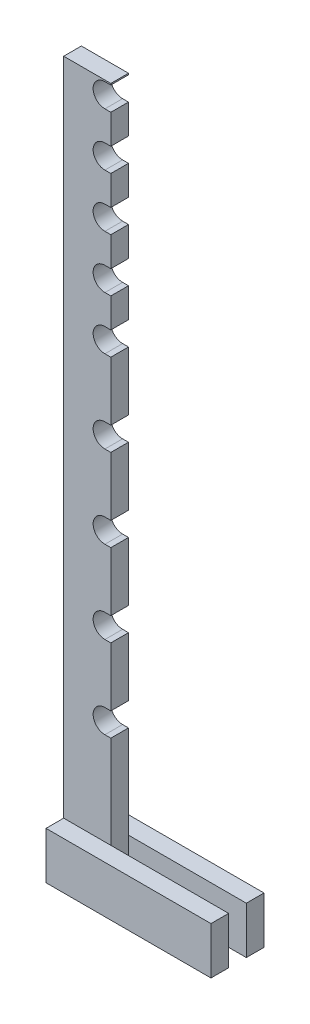
SolidWorks part; units mm, degrees
material "Maple"
ref_plane "Front" through (0, 0, 0) normal (0, 0, 1) x (1, 0, 0)
ref_plane "Top" through (0, 0, 0) normal (0, 1, 0) x (1, 0, 0)
ref_plane "Right" through (0, 0, 0) normal (1, 0, 0) x (0, 0, -1)
sketch "Sketch1" plane through (0, 0, 0) normal (0, 0, 1) x (1, 0, 0)
  line L10 (0, 0) -> (50.8, 0)
  line L14 (0, 0) -> (0, 762)
  line L15 (0, 762) -> (50.8, 762)
  line L16 (50.8, 0) -> (50.8, 762)
  dimension "D1" = 762
  dimension "D2" = 50.8
extrude "Boss-Extrude1" add sketch "Sketch1" along normal mid plane 19.05
sketch "Sketch3" plane through (0, 0, 9.525) normal (0, 0, 1) x (1, 0, 0)
  line L1 (0, 0) -> (177.8, 0)
  line L2 (0, 0) -> (0, 50.8)
  line L3 (0, 50.8) -> (177.8, 50.8)
  line L4 (177.8, 0) -> (177.8, 50.8)
  dimension "D1" = 50.8
  dimension "D2" = 177.8
extrude "Boss-Extrude2" add sketch "Sketch3" along normal blind 19.05 separate body
mirror "Mirror1" about plane through (0, 0, 0) normal (0, 0, 1) of bodies 182
sketch "Sketch2" plane through (0, 0, 9.525) normal (0, 0, 1) x (1, 0, 0)
  line L2 (44.45, 163.576) -> (50.8, 163.576) construction
  line L3 (50.8, 0) -> (50.8, 762) construction
  line L4 (44.45, 163.576) -> (44.45, 762) construction
  line L5 (50.8, 762) -> (0, 762) construction
  line L7 (44.45, 176.276) -> (50.8, 176.276)
  line L8 (44.45, 150.876) -> (50.8, 150.876)
  line L9 (50.8, 176.276) -> (50.8, 150.876)
  arc A0 (44.45, 176.276) -> (44.45, 150.876) centre (44.45, 163.576) ccw
  dimension "D1" = 25.4
  dimension "D2" = 163.576
  dimension "D3" = 6.35
extrude "Cut-Extrude1" cut sketch "Sketch2" against normal through all
pattern_linear "LPattern1" [suppressed] count 9 spacing 71.628 of bodies 180
pattern_linear "LPattern4" [suppressed] count 6 spacing 50.8 of bodies 180
sketch "Sketch4" [suppressed] plane through (0, 0, -9.525) normal (0, 0, -1) x (-1, 0, 0)
  line L0 (-44.45, 404.876) -> (-50.8, 404.876) construction
  line L1 (-44.45, 404.876) -> (-50.8, 404.876)
  line L2 (-50.8, 430.276) -> (-44.45, 430.276) construction
  line L3 (-50.8, 430.276) -> (-44.45, 430.276)
  line L4 (-50.8, 430.276) -> (-50.8, 404.876)
  line L5 (-50.8, 531.876) -> (-50.8, 506.476)
  line L6 (-44.45, 506.476) -> (-50.8, 506.476)
  line L7 (-50.8, 531.876) -> (-44.45, 531.876)
  line L8 (-50.8, 633.476) -> (-50.8, 608.076)
  line L9 (-44.45, 608.076) -> (-50.8, 608.076)
  line L10 (-50.8, 633.476) -> (-44.45, 633.476)
  line L11 (-50.8, 735.076) -> (-50.8, 709.676)
  line L12 (-44.45, 709.676) -> (-50.8, 709.676)
  line L13 (-50.8, 735.076) -> (-44.45, 735.076)
  arc A0 (-44.45, 404.876) -> (-44.45, 430.276) centre (-44.45, 417.576) ccw construction
  arc A1 (-44.45, 404.876) -> (-44.45, 430.276) centre (-44.45, 417.576) ccw
  arc A2 (-44.45, 506.476) -> (-44.45, 531.876) centre (-44.45, 519.176) ccw
  arc A3 (-44.45, 608.076) -> (-44.45, 633.476) centre (-44.45, 620.776) ccw
  arc A4 (-44.45, 709.676) -> (-44.45, 735.076) centre (-44.45, 722.376) ccw
  dimension "D2" = 101.6
  dimension "D1" = 4
extrude "Cut-Extrude2" [suppressed] cut sketch "Sketch4" against normal through all
pattern_linear "LPattern5" [suppressed] count 2 spacing 38.1 of bodies 185
pattern_linear "LPattern6" count 5 spacing 88.9 along (0, 1, 0) of "Cut-Extrude1"
sketch "Sketch5" plane through (0, 0, -9.525) normal (0, 0, -1) x (-1, 0, 0)
  line L0 (-44.45, 531.876) -> (-50.8, 531.876) construction
  line L1 (-44.45, 531.876) -> (-50.8, 531.876)
  line L2 (-50.8, 506.476) -> (-44.45, 506.476) construction
  line L3 (-50.8, 506.476) -> (-44.45, 506.476)
  line L4 (-50.8, 531.876) -> (-50.8, 506.476)
  line L5 (-50.8, 589.026) -> (-50.8, 563.626)
  line L6 (-50.8, 563.626) -> (-44.45, 563.626)
  line L7 (-44.45, 589.026) -> (-50.8, 589.026)
  line L8 (-50.8, 646.176) -> (-50.8, 620.776)
  line L9 (-50.8, 620.776) -> (-44.45, 620.776)
  line L10 (-44.45, 646.176) -> (-50.8, 646.176)
  line L11 (-50.8, 703.326) -> (-50.8, 677.926)
  line L12 (-50.8, 677.926) -> (-44.45, 677.926)
  line L13 (-44.45, 703.326) -> (-50.8, 703.326)
  line L14 (-50.8, 760.476) -> (-50.8, 735.076)
  line L15 (-50.8, 735.076) -> (-44.45, 735.076)
  line L16 (-44.45, 760.476) -> (-50.8, 760.476)
  arc A0 (-44.45, 506.476) -> (-44.45, 531.876) centre (-44.45, 519.176) ccw construction
  arc A1 (-44.45, 506.476) -> (-44.45, 531.876) centre (-44.45, 519.176) ccw
  arc A2 (-44.45, 563.626) -> (-44.45, 589.026) centre (-44.45, 576.326) ccw
  arc A3 (-44.45, 620.776) -> (-44.45, 646.176) centre (-44.45, 633.476) ccw
  arc A4 (-44.45, 677.926) -> (-44.45, 703.326) centre (-44.45, 690.626) ccw
  arc A5 (-44.45, 735.076) -> (-44.45, 760.476) centre (-44.45, 747.776) ccw
  dimension "D2" = 57.15
  dimension "D1" = 5
extrude "Cut-Extrude3" cut sketch "Sketch5" against normal through all
